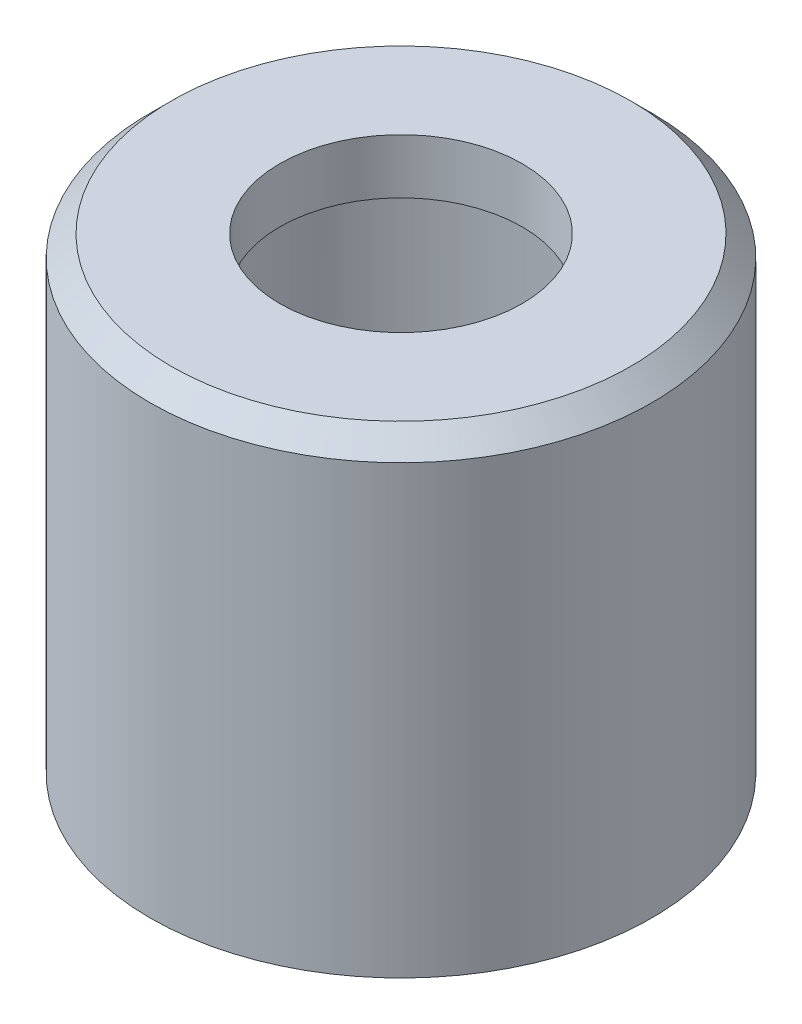
SolidWorks part; units mm, degrees
ref_plane "Front Plane" through (0, 0, 0) normal (0, 0, 1) x (1, 0, 0)
ref_plane "Top Plane" through (0, 0, 0) normal (0, 1, 0) x (1, 0, 0)
ref_plane "Right Plane" through (0, 0, 0) normal (1, 0, 0) x (0, 0, -1)
sketch "Sketch1" plane through (0, 0, 0) normal (0, 1, 0) x (1, 0, 0)
  circle A0 centre (0, 0) radius 2.98
  dimension "D1" = 5.96
extrude "Boss-Extrude1" add sketch "Sketch1" along normal blind 5.55
sketch "Sketch2" plane through (0, 0, 0) normal (0, -1, 0) x (1, 0, 0)
  circle A0 centre (0, 0) radius 2.5
  dimension "D1" = 5
extrude "Cut-Extrude1" cut sketch "Sketch2" against normal blind 4.9
sketch "Sketch3" plane through (0, 5.55, 0) normal (0, 1, 0) x (1, 0, 0)
  circle A0 centre (0, 0) radius 1.44
  dimension "D1" = 2.88
extrude "Cut-Extrude2" cut sketch "Sketch3" against normal through all
chamfer "Chamfer1" distance 0.25 angle 45 1 edges at (0, 5.55, 2.98)
thread "Thread1" pitch 0.8 method cut profile "Thread Profile1" start angle 0, offset 0, length 2, pitch 0.8, diameter 5
ref_plane "Plane1" through (2.5, 0, 0) normal (0, 0, 1) x (1, 0, 0)
sketch "Thread Profile1" plane through (2.5, 0, 0) normal (0, 0, 1) x (1, 0, 0)
  line L0 (0, 0) -> (0, 0.8) construction
  line L1 (0, 0) -> (0.433, 0.25)
  line L2 (0.433, 0.25) -> (0.433, 0.35)
  line L3 (0.433, 0.35) -> (0, 0.6)
  line L4 (0.433, 0.3) -> (0, 0.3) construction
  line L11 (0, 0) -> (0, 0.6)
  point P2 (0, 0)
  dimension "Pitch" = 0.8
  dimension "Profile_Angle" = 60
  dimension "Profile_Land" = 0.1
  dimension "Profile_Height" = 0.433
